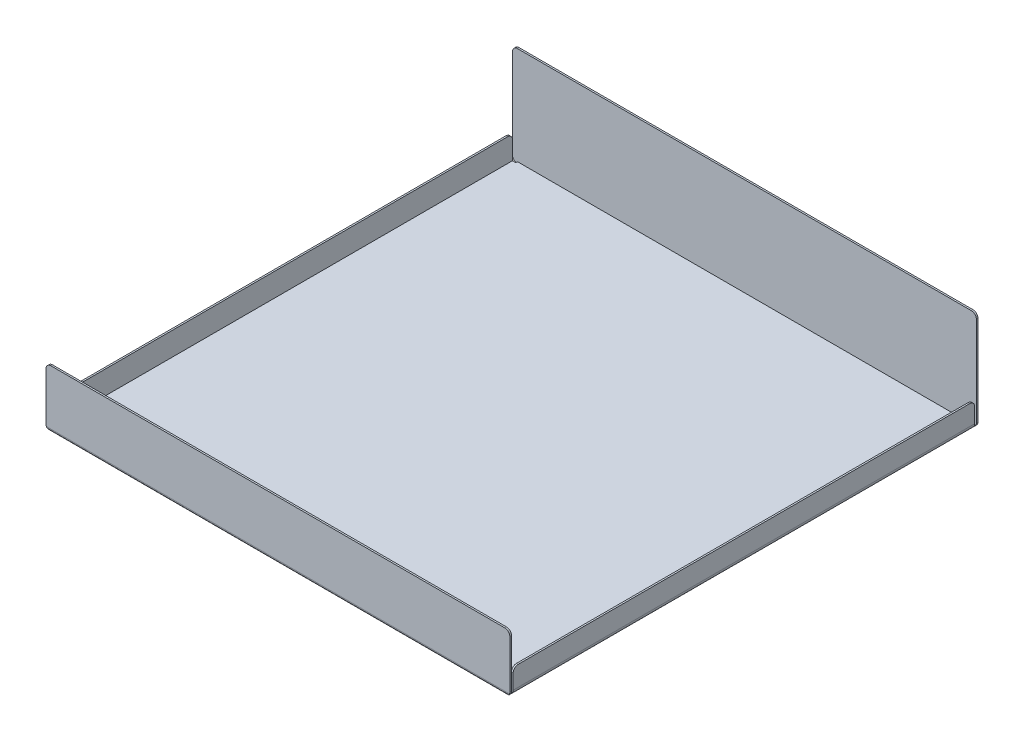
SolidWorks part; units mm, degrees
ref_plane "Front Plane" through (0, 0, 0) normal (0, 0, 1) x (1, 0, 0)
ref_plane "Top Plane" through (0, 0, 0) normal (0, 1, 0) x (1, 0, 0)
ref_plane "Right Plane" through (0, 0, 0) normal (1, 0, 0) x (0, 0, -1)
sketch "Sketch6" plane through (0, 0, 0) normal (0, 1, 0) x (1, 0, 0)
  line L1 (0, -162.3156) -> (279.4, -162.3156)
  line L2 (0, -162.3156) -> (0, 119.6844)
  line L3 (0, 119.6844) -> (279.4, 119.6844)
  line L4 (279.4, -162.3156) -> (279.4, 119.6844)
  dimension "D1" = 282
  dimension "D2" = 279.4
extrude "Boss-Extrude2" add sketch "Sketch6" along normal blind 60
sketch "Sketch8" plane through (0, 0, 0) normal (1, 0, 0) x (0, 0, -1)
  line L0 (-162.3156, 35) -> (-161.3156, 35)
  line L1 (-162.3156, 60) -> (-162.3156, 0) construction
  line L2 (-161.3156, 35) -> (-161.3156, 15)
  line L3 (-161.3156, 15) -> (118.6844, 15)
  line L4 (118.6844, 15) -> (118.6844, 60)
  line L5 (-162.3156, 60) -> (119.6844, 60) construction
  line L6 (118.6844, 60) -> (-162.3156, 60)
  line L7 (-162.3156, 60) -> (-162.3156, 35)
  line L8 (119.6844, 60) -> (119.6844, 0) construction
  line L9 (-162.3156, 0) -> (119.6844, 0) construction
  dimension "D1" = 1
  dimension "D2" = 1
  dimension "D3" = 15
  dimension "D4" = 35
extrude "Cut-Extrude7" cut sketch "Sketch8" against normal blind 60 and the other way through all from offset 30
shell "Shell1" thickness 1
sketch "Sketch9" plane through (0, 0, -119.6844) normal (0, 0, -1) x (-1, 0, 0)
  line L0 (-279.4, 60) -> (0, 60) construction
  line L1 (-279.4, 60) -> (-279.4, 0) construction
  line L2 (-279.4, 0) -> (0, 0) construction
  line L3 (0, 60) -> (0, 0) construction
  line L4 (-276.4, 60) -> (-3, 60)
  line L5 (-279.4, 57) -> (-279.4, 3)
  line L6 (-276.4, 0) -> (-3, 0)
  line L7 (0, 57) -> (0, 3)
  arc A0 (-276.4, 0) -> (-279.4, 3) centre (-276.4, 3) cw
  arc A1 (-3, 0) -> (0, 3) centre (-3, 3) ccw
  arc A2 (0, 57) -> (-3, 60) centre (-3, 57) ccw
  arc A3 (-279.4, 57) -> (-276.4, 60) centre (-276.4, 57) cw
  dimension "D1" = 3
extrude "Cut-Extrude8" cut sketch "Sketch9" against normal through all flip side to cut
sketch "Sketch10" plane through (0, 0, 162.3156) normal (0, 0, 1) x (1, 0, 0)
  line L0 (279.4, 35) -> (0, 35) construction
  line L1 (279.4, 35) -> (279.4, 3) construction
  line L2 (3, 0) -> (276.4, 0) construction
  line L3 (0, 35) -> (0, 3) construction
  line L4 (276.4, 35) -> (3, 35)
  line L5 (279.4, 32) -> (279.4, 3)
  line L6 (3, 0) -> (276.4, 0)
  line L7 (0, 32) -> (0, 3)
  arc A0 (276.4, 0) -> (279.4, 3) centre (276.4, 3) ccw construction
  arc A1 (0, 3) -> (3, 0) centre (3, 3) ccw construction
  arc A2 (276.4, 0) -> (279.4, 3) centre (276.4, 3) ccw
  arc A3 (0, 3) -> (3, 0) centre (3, 3) ccw
  arc A4 (276.4, 35) -> (279.4, 32) centre (276.4, 32) cw
  arc A5 (0, 32) -> (3, 35) centre (3, 32) cw
  dimension "D1" = 3
extrude "Cut-Extrude9" cut sketch "Sketch10" against normal up to surface (1 mm away) flip side to cut
sketch "Sketch11" plane through (279.4, 0, 0) normal (1, 0, 0) x (0, 0, -1)
  line L0 (-162.3156, 0) -> (119.6844, 0) construction
  line L1 (-161.3156, 15) -> (-157.3156, 15)
  line L2 (-161.3156, 15) -> (-161.3156, 1.9)
  line L3 (-160.4156, 1) -> (-160.3156, 1)
  line L4 (-160.3156, 12) -> (-160.3156, 1)
  line L6 (118.6844, 15) -> (114.6844, 15)
  line L7 (118.6844, 15) -> (118.6844, 1.9)
  line L8 (117.7844, 1) -> (117.6844, 1)
  line L9 (117.6844, 12) -> (117.6844, 1)
  arc A0 (117.7844, 1) -> (118.6844, 1.9) centre (117.7844, 1.9) ccw
  arc A1 (-161.3156, 1.9) -> (-160.4156, 1) centre (-160.4156, 1.9) ccw
  arc A2 (117.6844, 12) -> (114.6844, 15) centre (114.6844, 12) ccw
  arc A3 (-160.3156, 12) -> (-157.3156, 15) centre (-157.3156, 12) cw
  dimension "D5" = 0.9
  dimension "D6" = 0.9
  dimension "D3" = 3
  dimension "D2" = 1
  dimension "D4" = 1
extrude "Cut-Extrude11" cut sketch "Sketch11" against normal through all
fillet "Fillet2" radius 2 2 edges at (139.7, 0, -119.6844) (139.7, 0, 162.3156)
sketch "Sketch12" plane through (0, 0, 0) normal (0, -1, 0) x (1, 0, 0)
  line L0 (0, 161.3156) -> (3, 161.3156) construction
  line L1 (0, 160.3156) -> (3, 160.3156)
  line L2 (0, 160.3156) -> (0, 161.3156)
  line L3 (0, 161.3156) -> (3, 161.3156)
  line L4 (3, 160.3156) -> (3, 161.3156)
  line L6 (279.4, 160.3156) -> (276.4275, 160.3156)
  line L7 (279.4, 160.3156) -> (279.4, 161.3156)
  line L8 (279.4, 161.3156) -> (276.4275, 161.3156)
  line L9 (276.4275, 160.3156) -> (276.4275, 161.3156)
  line L10 (279.3788, -118.6844) -> (276.4, -118.6844)
  line L11 (279.3788, -118.6844) -> (279.3788, -117.6844)
  line L12 (279.3788, -117.6844) -> (276.4, -117.6844)
  line L13 (276.4, -118.6844) -> (276.4, -117.6844)
  line L14 (0, -118.6844) -> (3, -118.6844)
  line L15 (0, -118.6844) -> (0, -117.6844)
  line L16 (0, -117.6844) -> (3, -117.6844)
  line L17 (3, -118.6844) -> (3, -117.6844)
extrude "Cut-Extrude12" cut sketch "Sketch12" against normal through all
